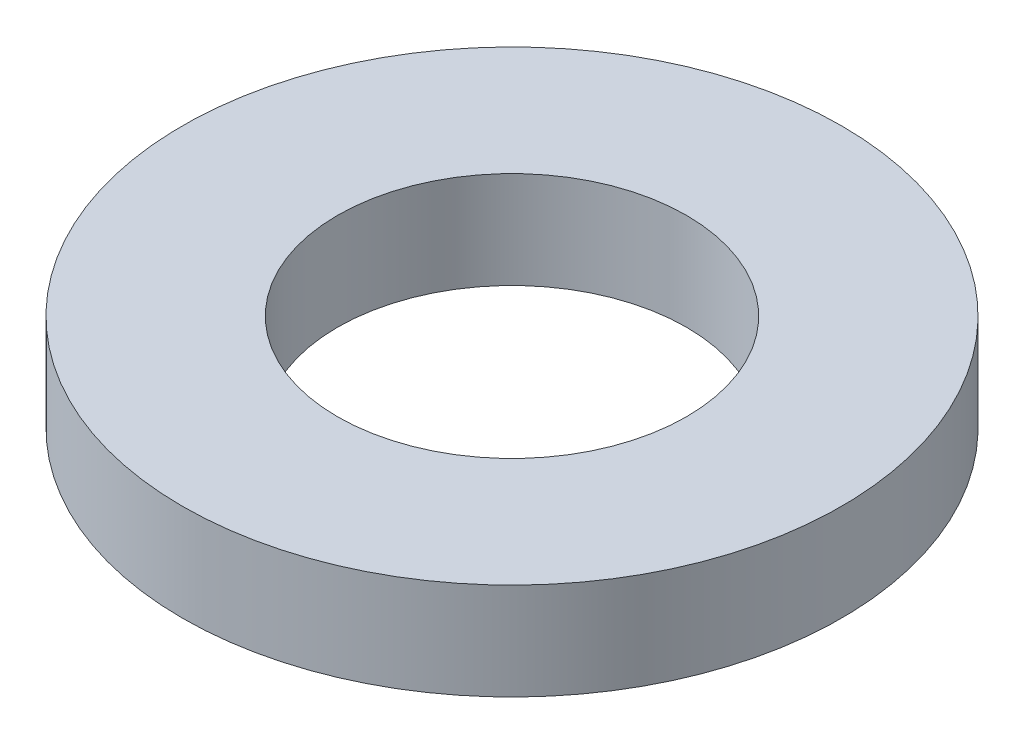
SolidWorks part; units mm, degrees
ref_plane "Front Plane" through (0, 0, 0) normal (0, 0, 1) x (1, 0, 0)
ref_plane "Top Plane" through (0, 0, 0) normal (0, 1, 0) x (1, 0, 0)
ref_plane "Right Plane" through (0, 0, 0) normal (1, 0, 0) x (0, 0, -1)
sketch "Sketch1" plane through (0, 0, 0) normal (0, 1, 0) x (1, 0, 0)
  circle A0 centre (0, 0) radius 85
  dimension "FLANGE_OD" = 170
extrude "Boss-Extrude1" add sketch "Sketch1" along normal blind 25
sketch "Sketch2" plane through (0, 0, 0) normal (0, 1, 0) x (1, 0, 0)
  circle A0 centre (0, 0) radius 45
  dimension "BORE_D" = 90
extrude "Cut-Extrude1" cut sketch "Sketch2" along normal through all
sketch "Sketch3" plane through (0, 25, 0) normal (0, 1, 0) x (1, 0, 0)
  circle A0 centre (0, 0) radius 31.7425 construction
  circle A1 centre (-31.7425, 0) radius 4.9626
  dimension "BOLT_D" = 9.9252
  dimension "BOLT_PCD" = 63.4849
extrude "Cut-Extrude2" cut sketch "Sketch3" against normal blind 15.4622 rebuild error yes
pattern_circular "CirPattern1" count 5 over 360 rebuild error yes
